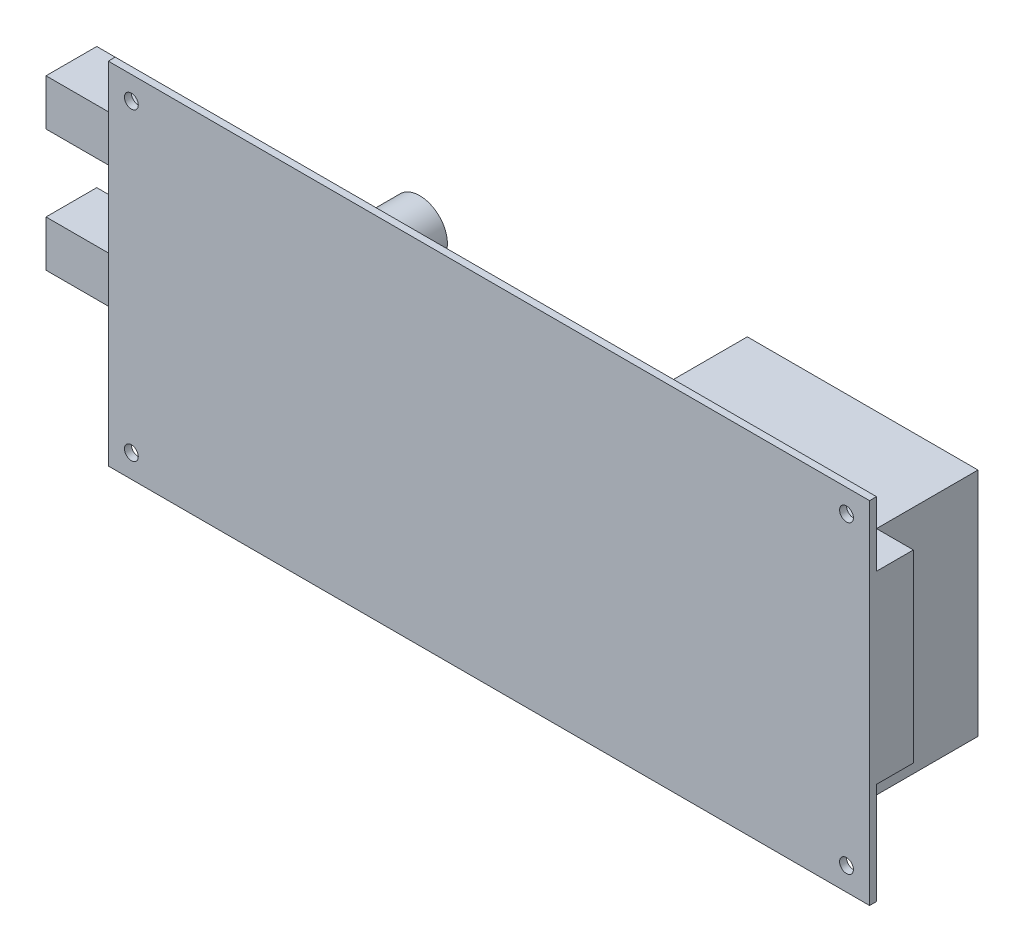
SolidWorks part; units mm, degrees
ref_plane "Front Plane" through (0, 0, 0) normal (0, 0, 1) x (1, 0, 0)
ref_plane "Top Plane" through (0, 0, 0) normal (0, 1, 0) x (1, 0, 0)
ref_plane "Right Plane" through (0, 0, 0) normal (1, 0, 0) x (0, 0, -1)
sketch "Sketch1" plane through (0, 0, 0) normal (0, 0, 1) x (1, 0, 0)
  line L1 (-35.2387, 26.9472) -> (129.7613, 26.9472)
  line L2 (-35.2387, 26.9472) -> (-35.2387, -49.0528)
  line L3 (-35.2387, -49.0528) -> (129.7613, -49.0528)
  line L4 (129.7613, 26.9472) -> (129.7613, -49.0528)
  dimension "D1" = 165
  dimension "D2" = 76
extrude "Boss-Extrude1" add sketch "Sketch1" along normal blind 1.5
sketch "Sketch2" plane through (0, 0, 1.5) normal (0, 0, 1) x (1, 0, 0)
  line L0 (129.7613, 26.9472) -> (-35.2387, 26.9472) construction
  line L1 (129.7613, -49.0528) -> (129.7613, 26.9472) construction
  line L2 (47.2613, 26.9472) -> (47.2613, -49.0528) construction
  line L3 (-35.2387, -49.0528) -> (129.7613, -49.0528) construction
  line L4 (-35.2387, -11.0528) -> (129.7613, -11.0528) construction
  line L5 (-35.2387, 26.9472) -> (-35.2387, -49.0528) construction
  circle A0 centre (124.7613, 21.9472) radius 1.5
  circle A1 centre (124.7613, -44.0528) radius 1.5
  circle A2 centre (-30.2387, -44.0528) radius 1.5
  circle A3 centre (-30.2387, 21.9472) radius 1.5
  dimension "D1" = 3
  dimension "D2" = 5
  dimension "D3" = 5
extrude "Cut-Extrude1" cut sketch "Sketch2" against normal up to next
sketch "Sketch3" plane through (0, 0, 0) normal (0, 0, -1) x (-1, 0, 0)
  line L0 (-129.7613, -49.0528) -> (-129.7613, 26.9472) construction
  line L1 (-129.7613, -27.0528) -> (-117.7613, -27.0528)
  line L2 (-129.7613, -27.0528) -> (-129.7613, 12.9472)
  line L3 (-129.7613, 12.9472) -> (-117.7613, 12.9472)
  line L4 (-117.7613, -27.0528) -> (-117.7613, 12.9472)
  line L5 (-129.7613, 26.9472) -> (35.2387, 26.9472) construction
  dimension "D1" = 12
  dimension "D2" = 40
  dimension "D3" = 14
extrude "Boss-Extrude2" add sketch "Sketch3" along normal blind 8
sketch "Sketch4" plane through (0, 0, 0) normal (0, 0, -1) x (-1, 0, 0)
  line L0 (35.2387, -49.0528) -> (-129.7613, -49.0528) construction
  line L1 (-69.7613, 10.9472) -> (-119.7613, 10.9472)
  line L2 (-69.7613, 10.9472) -> (-69.7613, -39.0528)
  line L3 (-69.7613, -39.0528) -> (-119.7613, -39.0528)
  line L4 (-119.7613, 10.9472) -> (-119.7613, -39.0528)
  line L5 (-129.7613, -49.0528) -> (-129.7613, -27.0528) construction
  dimension "D1" = 50
  dimension "D2" = 50
  dimension "D3" = 10
  dimension "D4" = 10
extrude "Boss-Extrude3" add sketch "Sketch4" along normal blind 32
sketch "Sketch5" plane through (0, 0, 0) normal (0, 0, -1) x (-1, 0, 0)
  line L0 (35.2387, 26.9472) -> (35.2387, -49.0528) construction
  line L1 (50.2387, 5.9472) -> (20.2387, 5.9472)
  line L2 (50.2387, 5.9472) -> (50.2387, 15.9472)
  line L3 (50.2387, 15.9472) -> (20.2387, 15.9472)
  line L4 (20.2387, 5.9472) -> (20.2387, 15.9472)
  line L5 (-129.7613, 26.9472) -> (35.2387, 26.9472) construction
  line L6 (20.2387, -20.5528) -> (50.2387, -20.5528)
  line L7 (20.2387, -20.5528) -> (20.2387, -10.5528)
  line L8 (20.2387, -10.5528) -> (50.2387, -10.5528)
  line L9 (50.2387, -20.5528) -> (50.2387, -10.5528)
  dimension "D1" = 15
  dimension "D2" = 10
  dimension "D3" = 30
  dimension "D4" = 26.5
  dimension "D5" = 11
extrude "Boss-Extrude4" add sketch "Sketch5" along normal blind 11
sketch "Sketch6" plane through (0, 0, 0) normal (0, 0, -1) x (-1, 0, 0)
  line L0 (-129.7613, 26.9472) -> (35.2387, 26.9472) construction
  line L1 (35.2387, 5.9472) -> (35.2387, -10.5528) construction
  circle A0 centre (-5.7613, 2.9472) radius 6
  dimension "D1" = 12
  dimension "D2" = 24
  dimension "D3" = 41
extrude "Boss-Extrude5" add sketch "Sketch6" along normal blind 25
sketch "Sketch7" plane through (0, 0, 1.5) normal (0, 0, 1) x (1, 0, 0)
  line L0 (129.7613, -49.0528) -> (129.7613, 26.9472) construction
  line L1 (129.7613, -11.0528) -> (-35.2387, -11.0528) construction
  line L2 (-35.2387, 26.9472) -> (-35.2387, -49.0528) construction
  line L3 (47.2613, 26.9472) -> (47.2613, -49.0528) construction
  line L4 (129.7613, 26.9472) -> (-35.2387, 26.9472) construction
  line L5 (-35.2387, -49.0528) -> (129.7613, -49.0528) construction
  circle A0 centre (124.7613, 21.9472) radius 3
  circle A1 centre (124.7613, 21.9472) radius 1.5 construction
  circle A3 centre (124.7613, -44.0528) radius 3
  circle A4 centre (-30.2387, 21.9472) radius 3
  circle A5 centre (-30.2387, -44.0528) radius 3
  dimension "D1" = 6
extrude "Boss-Extrude6" [suppressed] add sketch "Sketch7" along normal blind 12
